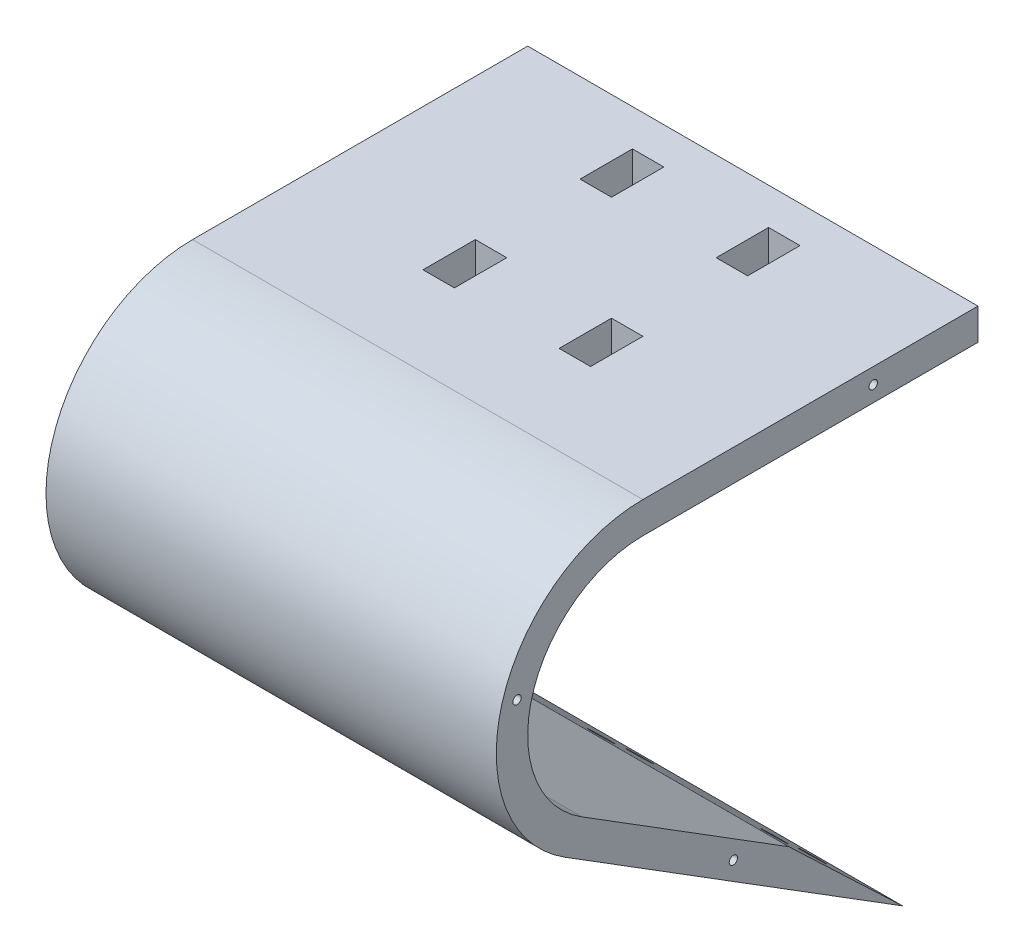
SolidWorks part; units mm, degrees
ref_plane "前视基准面" through (0, 0, 0) normal (0, 0, 1) x (1, 0, 0)
ref_plane "上视基准面" through (0, 0, 0) normal (0, 1, 0) x (1, 0, 0)
ref_plane "右视基准面" through (0, 0, 0) normal (1, 0, 0) x (0, 0, -1)
other "Configuration Table"
sketch "草图2" plane through (0, 0, 0) normal (0, 1, 0) x (1, 0, 0)
  line L15 (-21.5, 0) -> (21.5, 0)
  line L16 (-21.5, 0) -> (-21.5, -32)
  line L17 (-21.5, -32) -> (21.5, -32)
  line L18 (21.5, 0) -> (21.5, -32)
  dimension "D1" = 43
  dimension "D2" = 32
extrude "凸台-拉伸1" add sketch "草图2" along normal blind 3
sketch "草图3" plane through (21.5, 0, 0) normal (1, 0, 0) x (0, 0, -1)
  line L1 (-37.8291, -20.3285) -> (-5.6033, -40.4655)
  line L2 (-37.8291, -20.3285) -> (-39.4189, -22.8727)
  line L3 (-39.4189, -22.8727) -> (-7.193, -43.0096)
  line L4 (-5.6033, -40.4655) -> (-7.193, -43.0096)
  line L5 (-37.8291, -20.3285) -> (-32, 0)
  line L6 (-32, 0) -> (-23.3397, 0)
  circle A0 centre (-32, -11) radius 14
  circle A1 centre (-32, -11) radius 11
  line M6 (-32, 3) -> (-32, 0)
  dimension "D1" = 28
  dimension "D2" = 3
  dimension "D3" = 32
  dimension "D4" = 38
extrude "凸台-拉伸2" add sketch "草图3" against normal up to surface (43 mm away) contours A1 A0 L2 M6 | L2 L3 L4 L1 region at (21.5, -21.4447, 38.8735) up to face at (-21.5, 1.5, 16)
sketch "草图4" plane through (0, 0, 0) normal (0, -1, 0) x (1, 0, 0)
  line L0 (21.5, 0) -> (-21.5, 0) construction
  line L1 (8, 3.5) -> (5, 3.5)
  line L2 (8, 3.5) -> (8, 8.5)
  line L3 (8, 8.5) -> (5, 8.5)
  line L4 (5, 3.5) -> (5, 8.5)
  line L5 (8, 18.5) -> (5, 18.5)
  line L6 (8, 18.5) -> (8, 23.5)
  line L7 (8, 23.5) -> (5, 23.5)
  line L8 (5, 18.5) -> (5, 23.5)
  line L9 (21.5, 32) -> (21.5, 0) construction
  line L10 (-21.5, 0) -> (-21.5, 32) construction
  line L11 (-5, 3.5) -> (-8, 3.5)
  line L12 (-5, 3.5) -> (-5, 8.5)
  line L13 (-5, 8.5) -> (-8, 8.5)
  line L14 (-8, 3.5) -> (-8, 8.5)
  line L15 (-8, 23.5) -> (-5, 23.5)
  line L16 (-8, 23.5) -> (-8, 18.5)
  line L17 (-8, 18.5) -> (-5, 18.5)
  line L18 (-5, 23.5) -> (-5, 18.5)
  dimension "D1" = 3
  dimension "D2" = 3.5
  dimension "D3" = 10
  dimension "D4" = 5
  dimension "D5" = 13.5
  dimension "D6" = 13.5
extrude "切除-拉伸1" cut sketch "草图4" against normal through all
sketch "草图5" plane through (21.5, 0, 0) normal (1, 0, 0) x (0, 0, -1)
  line L1 (-8.4735, -40.4407) -> (-60.8019, -7.7423) construction
  line L2 (-5.6033, -40.4655) -> (-7.193, -43.0096) construction
  line L3 (-50.2628, 1.5) -> (17.7951, 1.5) construction
  line L4 (0, 3) -> (0, 0) construction
  line L5 (-75.5927, 1.5) -> (-32, -11) construction
  circle A0 centre (-10, 1.5) radius 0.4
  circle A1 centre (-44.0158, -7.5545) radius 0.4
  circle A2 centre (-23.3591, -31.1391) radius 0.4
  circle A3 centre (-32, -11) radius 11 construction
  arc A4 (-32, 0) -> (-37.8291, -20.3285) centre (-32, -11) ccw construction
  point P11 (-6.3982, -41.7375)
  point P15 (0, 1.5)
  point P16 (0, 1.5)
  point P17 (0, 1.5)
  dimension "D1" = 0.8
  dimension "D2" = 12.5
  dimension "D3" = 10
  dimension "D4" = 20
extrude "切除-拉伸2" cut sketch "草图5" against normal blind 3
extrude "切除-拉伸3" cut sketch "草图5<3>" along normal blind 3 from surface starting at face at (-21.5, -14.4606, 21.4315)
sketch "草图5<3>" plane through (21.5, 0, 0) normal (1, 0, 0) x (0, 0, -1) same geometry as "草图5"
sketch "草图6" plane through (21.5, 0, 0) normal (1, 0, 0) x (0, 0, -1)
  line L0 (-7.193, -43.0096) -> (-18.067, -32.6773)
  line L1 (-37.8291, -20.3285) -> (-5.6033, -40.4655) construction
  line M10 (-7.193, -43.0096) -> (-5.6033, -40.4655)
  line M11 (-5.6033, -40.4655) -> (-37.8291, -20.3285)
  dimension "D1" = 15
extrude "切除-拉伸4" cut sketch "草图6" along normal through all and the other way through all contours L0 M10 M11 region at (21.5, -38.7174, 10.2878)
sketch "草图8" plane through (0, -26.1944, 24.8897) normal (0, 0.7249, -0.6888) x (1, 0, 0)
  circle A0 centre (16.5, 19.4115) radius 1.1
  circle A1 centre (16.5, 14.4115) radius 1.1
  circle A2 centre (0, 14.4115) radius 1.1
  circle A3 centre (0, 19.4115) radius 1.1
  circle A4 centre (-16.5, 19.4115) radius 1.1
  circle A5 centre (-16.5, 14.4115) radius 1.1
  point P12 (0, 0)
  dimension "D1" = 2.2
extrude "切除-拉伸5" cut sketch "草图8" against normal through all
